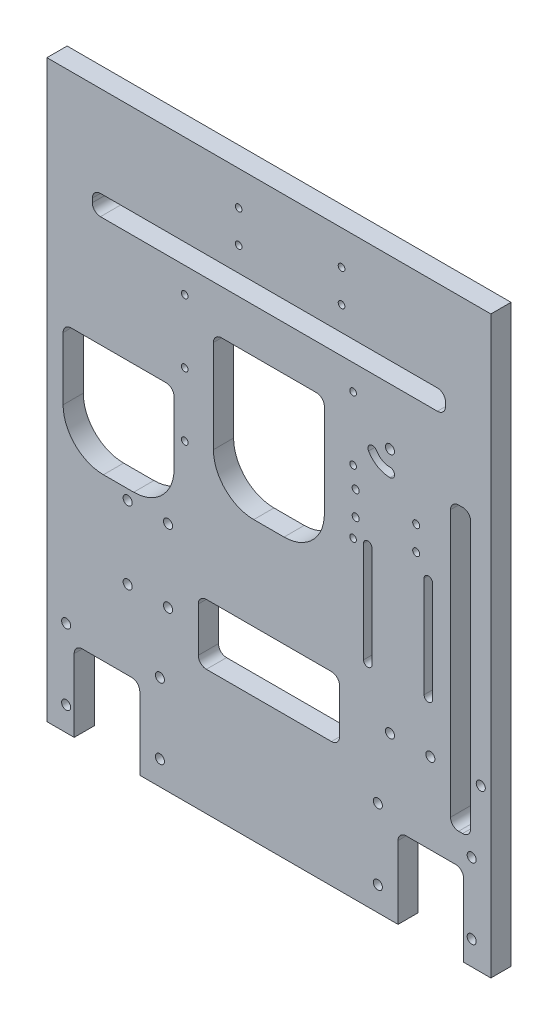
SolidWorks part; units mm, degrees
ref_plane "Front" through (0, 0, 0) normal (0, 0, 1) x (1, 0, 0)
ref_plane "Top" through (0, 0, 0) normal (0, 1, 0) x (1, 0, 0)
ref_plane "Right" through (0, 0, 0) normal (1, 0, 0) x (0, 0, -1)
sketch "Esquisse1" plane through (0, 0, 0) normal (0, 0, 1) x (1, 0, 0)
  line L1 (0, 0) -> (220, 0)
  line L2 (0, 0) -> (0, 285)
  line L3 (0, 285) -> (220, 285)
  line L4 (220, 0) -> (220, 285)
  dimension "D1" = 220
  dimension "D2" = 285
extrude "Boss.-Extru.1" add sketch "Esquisse1" along normal blind 10
sketch "Esquisse2" plane through (0, 0, 0) normal (0, -1, 0) x (1, 0, 0)
  line L0 (0, 5) -> (220, 5) construction
  line L1 (0, 10) -> (0, 0) construction
  line L2 (220, 10) -> (220, 0) construction
  line L3 (110, 5) -> (110, 28.0559) construction
  circle A0 centre (110, 5) radius 2
  circle A1 centre (213, 5) radius 2
  circle A2 centre (7, 5) radius 2
  dimension "D1" = 4
  dimension "D2" = 103
extrude "Enlèv. mat.-Extru.1" cut sketch "Esquisse2" against normal blind 8
sketch "Esquisse3" plane through (0, 0, 10) normal (0, 0, 1) x (1, 0, 0)
  line L0 (110, 0) -> (110, 285) construction
  line L1 (0, 0) -> (220, 0) construction
  line L2 (220, 285) -> (0, 285) construction
  line L3 (82.5, 208) -> (137.5, 208)
  line L4 (137.5, 208) -> (137.5, 138)
  line L5 (137.5, 138) -> (82.5, 138)
  line L6 (82.5, 208) -> (82.5, 138)
  line L8 (8, 175) -> (63, 175)
  line L9 (8, 175) -> (8, 120)
  line L10 (8, 120) -> (63, 120)
  line L11 (63, 175) -> (63, 120)
  line L12 (200, 55) -> (210, 55)
  line L13 (200, 55) -> (200, 195)
  line L14 (200, 195) -> (210, 195)
  line L15 (210, 55) -> (210, 195)
  point P11 (110, 138)
  point P12 (110, 208)
  dimension "D1" = 70
  dimension "D2" = 55
  dimension "D3" = 138
  dimension "D4" = 55
  dimension "D5" = 47
  dimension "D6" = 55
  dimension "D7" = 120
  dimension "D8" = 140
  dimension "D9" = 55
  dimension "D10" = 90
  dimension "D11" = 10
extrude "Enlèv. mat.-Extru.2" cut sketch "Esquisse3" against normal through all both and the other way through all
sketch "Esquisse5" plane through (0, 0, 10) normal (0, 0, 1) x (1, 0, 0)
  line L0 (110, 230) -> (110, 0) construction
  line L1 (22.5, 240) -> (197.5, 240)
  line L2 (22.5, 240) -> (22.5, 230)
  line L3 (22.5, 230) -> (197.5, 230)
  line L4 (197.5, 240) -> (197.5, 230)
  line L5 (0, 0) -> (220, 0) construction
  dimension "D1" = 175
  dimension "D2" = 10
  dimension "D3" = 230
extrude "Enlèv. mat.-Extru.3" cut sketch "Esquisse5" against normal through all both and the other way through all
sketch "Esquisse6" plane through (0, 0, 10) normal (0, 0, 1) x (1, 0, 0)
  line L0 (170, 80) -> (190, 80) construction
  line L1 (0, 0) -> (220, 0) construction
  line L2 (137.5, 138) -> (82.5, 138) construction
  line L3 (215, 80) -> (190, 80) construction
  line L4 (168, 193.9299) -> (168, 170.25) construction
  line L5 (186.4274, 170.25) -> (149.5726, 170.25) construction
  line L6 (0, 285) -> (0, 0) construction
  circle A0 centre (190, 80) radius 2.25
  circle A1 centre (170, 80) radius 2.25
  circle A2 centre (215, 80) radius 2.25
  circle A3 centre (153, 176.25) radius 1.75
  circle A4 centre (183, 176.25) radius 1.75
  circle A5 centre (183, 164.25) radius 1.75
  circle A6 centre (153, 164.25) radius 1.75
  point P8 (110, 138)
  dimension "D1" = 4.5
  dimension "D3" = 80
  dimension "D6" = 30
  dimension "D7" = 12
  dimension "D8" = 3.5
  dimension "D2" = 20
  dimension "D4" = 60
  dimension "D5" = 25
  dimension "D9" = 168
  dimension "D10" = 170.25
extrude "Enlèv. mat.-Extru.4" cut sketch "Esquisse6" against normal through all both and the other way through all
sketch "Esquisse7" plane through (0, 0, 10) normal (0, 0, 1) x (1, 0, 0)
  line L0 (110, 0) -> (110, 285) construction
  line L1 (0, 0) -> (220, 0) construction
  line L2 (220, 285) -> (0, 285) construction
  line L3 (68.285, 186) -> (68.285, 217.4) construction
  line L4 (68.285, 186) -> (110, 186) construction
  line L5 (151.715, 186) -> (151.715, 217.4) construction
  line L6 (95, 268) -> (120.5, 268) construction
  line L7 (120.5, 268) -> (120.5, 260) construction
  line L8 (120.5, 260) -> (137.9818, 260) construction
  line L9 (95, 252) -> (120.5, 252) construction
  line L10 (22.5, 240) -> (197.5, 240) construction
  circle A0 centre (68.285, 217.4) radius 1.65
  circle A1 centre (68.285, 186) radius 1.65
  circle A2 centre (68.285, 154.6) radius 1.65
  circle A3 centre (151.715, 154.6) radius 1.65
  circle A4 centre (151.715, 186) radius 1.65
  circle A5 centre (151.715, 217.4) radius 1.65
  circle A6 centre (95, 268) radius 1.65
  circle A7 centre (146, 268) radius 1.65
  circle A8 centre (146, 252) radius 1.65
  circle A9 centre (95, 252) radius 1.65
  dimension "D1" = 31.4
  dimension "D2" = 3.3
  dimension "D5" = 16
  dimension "D6" = 51
  dimension "D9" = 3.3
  dimension "D7" = 15
  dimension "D3" = 83.43
  dimension "D4" = 186
  dimension "D8" = 20
extrude "Enlèv. mat.-Extru.5" cut sketch "Esquisse7" against normal through all both and the other way through all
sketch "Esquisse8" plane through (0, 0, 10) normal (0, 0, 1) x (1, 0, 0)
  line L0 (110, 0) -> (110, 285) construction
  line L1 (0, 0) -> (220, 0) construction
  line L2 (220, 285) -> (0, 285) construction
  line L3 (174, 0) -> (174, 40)
  line L4 (13.5, 0) -> (46, 0)
  line L5 (13.5, 0) -> (13.5, 40)
  line L6 (13.5, 40) -> (46, 40)
  line L7 (46, 0) -> (46, 40)
  line L8 (206.5, 40) -> (174, 40)
  line L9 (206.5, 0) -> (206.5, 40)
  line L10 (206.5, 0) -> (174, 0)
  dimension "D1" = 128
  dimension "D2" = 32.5
  dimension "D3" = 40
extrude "Enlèv. mat.-Extru.6" cut sketch "Esquisse8" against normal through all both and the other way through all
fillet "Congé1" radius 20 4 edges at (137.5, 138, 5) (82.5, 138, 5) (63, 120, 5) (8, 120, 5)
sketch "Esquisse9" plane through (0, 0, 10) normal (0, 0, 1) x (1, 0, 0)
  line L0 (189, 155) -> (189, 105) construction
  line L1 (191.1, 155) -> (191.1, 105)
  line L2 (186.9, 155) -> (186.9, 105)
  line L3 (189, 130) -> (159, 130) construction
  line L4 (174, 130) -> (174, 131.5076) construction
  line L5 (159, 105) -> (159, 155) construction
  line L6 (156.9, 105) -> (156.9, 155)
  line L7 (161.1, 105) -> (161.1, 155)
  line L9 (210, 55) -> (200, 55) construction
  line L10 (200, 55) -> (200, 195) construction
  arc A0 (191.1, 155) -> (186.9, 155) centre (189, 155) ccw
  arc A1 (186.9, 105) -> (191.1, 105) centre (189, 105) ccw
  arc A2 (156.9, 105) -> (161.1, 105) centre (159, 105) ccw
  arc A3 (161.1, 155) -> (156.9, 155) centre (159, 155) ccw
  point P2 (189, 130)
  point P13 (159, 130)
  dimension "D1" = 4.2
  dimension "D2" = 30
  dimension "D3" = 11
  dimension "D4" = 50
  dimension "D5" = 50
extrude "Enlèv. mat.-Extru.7" cut sketch "Esquisse9" against normal through all both and the other way through all
sketch "Esquisse10" plane through (0, 0, 10) normal (0, 0, 1) x (1, 0, 0)
  line L0 (9.5, 0) -> (9.5, 52.9697) construction
  line L1 (0, 0) -> (13.5, 0) construction
  line L2 (0, 285) -> (0, 0) construction
  line L3 (110, 0) -> (110, 48.9194) construction
  line L4 (46, 0) -> (174, 0) construction
  line L5 (32.75, 0) -> (32.75, 52.9697) construction
  circle A0 centre (9.5, 12) radius 2.25
  circle A1 centre (9.5, 47) radius 2.25
  circle A2 centre (210.5, 47) radius 2.25
  circle A3 centre (210.5, 12) radius 2.25
  circle A4 centre (56, 47) radius 2.25
  circle A5 centre (56, 12) radius 2.25
  circle A6 centre (164, 12) radius 2.25
  circle A7 centre (164, 47) radius 2.25
  dimension "D2" = 4.5
  dimension "D3" = 35
  dimension "D4" = 12
  dimension "D5" = 46.5
  dimension "D1" = 9.5
extrude "Enlèv. mat.-Extru.8" cut sketch "Esquisse10" against normal through all both and the other way through all
sketch "Esquisse11" plane through (0, 0, 10) normal (0, 0, 1) x (1, 0, 0)
  line L0 (110, 62) -> (110, 0) construction
  line L1 (75, 92) -> (145, 92)
  line L2 (75, 92) -> (75, 62)
  line L3 (75, 62) -> (145, 62)
  line L4 (145, 92) -> (145, 62)
  line L5 (46, 0) -> (174, 0) construction
  dimension "D1" = 70
  dimension "D2" = 30
  dimension "D3" = 62
extrude "Enlèv. mat.-Extru.9" cut sketch "Esquisse11" against normal through all both and the other way through all
fillet "Congé2" radius 4 20 edges at (137.5, 208, 5) (82.5, 208, 5) (197.5, 230, 5) (197.5, 240, 5) (22.5, 240, 5) (22.5, 230, 5) (63, 175, 5) (8, 175, 5) (200, 195, 5) (210, 195, 5) (210, 55, 5) (200, 55, 5) (206.5, 40, 5) (174, 40, 5) (46, 40, 5) (13.5, 40, 5) (75, 62, 5) (145, 62, 5) (145, 92, 5) (75, 92, 5)
sketch "Esquisse12" plane through (0, 0, 10) normal (0, 0, 1) x (1, 0, 0)
  line L0 (220, 0) -> (220, 285) construction
  line L1 (46, 0) -> (174, 0) construction
  line L2 (170, 202) -> (161.3397, 197) construction
  line L3 (170, 192) -> (170, 202) construction
  circle A0 centre (170, 202) radius 2.25
  arc A1 (161.3397, 197) -> (170, 192) centre (170, 202) ccw construction
  arc A2 (159.3912, 195.875) -> (170, 189.75) centre (170, 202) ccw
  arc A3 (163.2883, 198.125) -> (170, 194.25) centre (170, 202) ccw
  arc A4 (163.2883, 198.125) -> (159.3912, 195.875) centre (161.3397, 197) ccw
  arc A5 (170, 189.75) -> (170, 194.25) centre (170, 192) ccw
  point P9 (165, 193.3397)
  point P14 (0, 0)
  point P15 (0, 0)
  point P16 (160.4471, 167.0434)
  point P17 (168.5373, 160.1076)
  dimension "D1" = 4.5
  dimension "D2" = 50
  dimension "D3" = 202
  dimension "D4" = 4.5
  dimension "D5" = 10
  dimension "D6" = 60
extrude "Enlèv. mat.-Extru.10" cut sketch "Esquisse12" against normal through all both and the other way through all
sketch "Esquisse13" plane through (0, 0, 10) normal (0, 0, 1) x (1, 0, 0)
  line L0 (50, 123.132) -> (50, 97) construction
  line L1 (50, 97) -> (30.3926, 97) construction
  line L2 (46, 0) -> (174, 0) construction
  line L3 (0, 285) -> (0, 0) construction
  circle A0 centre (40, 115) radius 2.25
  circle A1 centre (60, 115) radius 2.25
  circle A2 centre (60, 79) radius 2.25
  circle A3 centre (40, 79) radius 2.25
  dimension "D1" = 36
  dimension "D2" = 20
  dimension "D3" = 4.5
  dimension "D4" = 97
  dimension "D5" = 40
extrude "Enlèv. mat.-Extru.11" cut sketch "Esquisse13" against normal through all both and the other way through all
